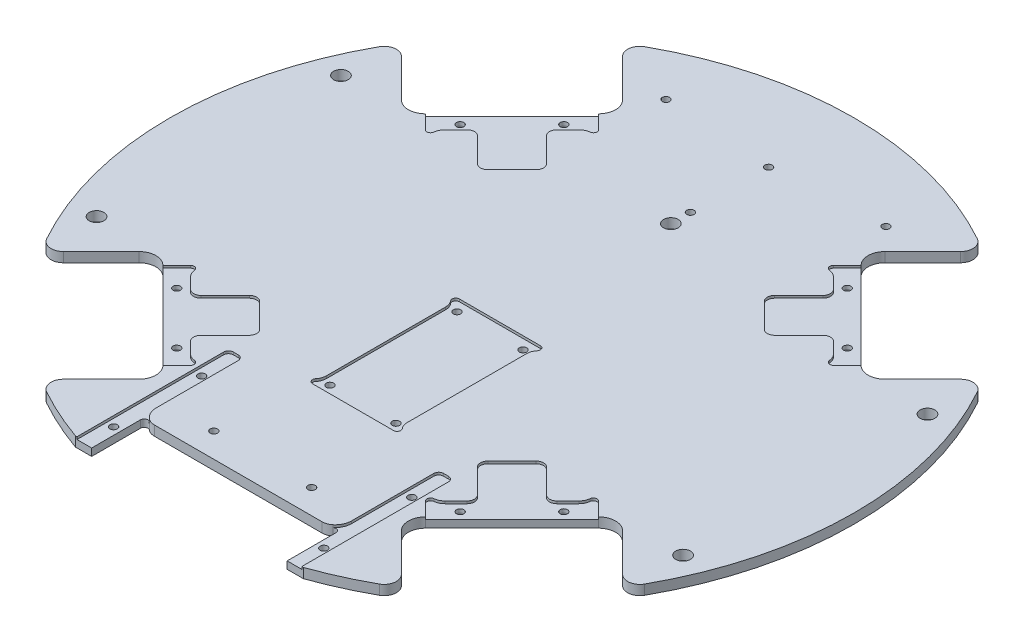
SolidWorks part; units mm, degrees
material "ABS PC"
ref_plane "Front Plane" through (0, 0, 0) normal (0, 0, 1) x (1, 0, 0)
ref_plane "Top Plane" through (0, 0, 0) normal (0, 1, 0) x (1, 0, 0)
ref_plane "Right Plane" through (0, 0, 0) normal (1, 0, 0) x (0, 0, -1)
sketch "Sketch1" plane through (0, 0, 0) normal (0, 1, 0) x (1, 0, 0)
  circle A0 centre (0, 0) radius 140
  dimension "D1" = 280
extrude "Boss-Extrude1" add sketch "Sketch1" along normal blind 4
sketch "Sketch7" plane through (0, 4, 0) normal (0, 1, 0) x (1, 0, 0)
  line L0 (-89.1308, -53.7048) -> (-53.7048, -89.1308)
  line L1 (-98.9596, -53.7048) -> (-121.6224, -76.3675)
  line L2 (-53.7048, -98.9596) -> (-76.3675, -121.6224)
  line L3 (-121.6224, -76.3675) -> (-76.3675, -121.6224)
  line L4 (0, 0) -> (-98.9949, -98.9949) construction
  line L7 (0, 0) -> (0, 130) construction
  circle A0 centre (0, 0) radius 140 construction
  arc A1 (-98.9596, -53.7048) -> (-89.1308, -53.7048) centre (-94.0452, -58.6192) cw
  arc A2 (-53.7048, -89.1308) -> (-53.7048, -98.9596) centre (-58.6192, -94.0452) cw
  dimension "D4" = 6.95
  dimension "D1" = 101
  dimension "D2" = 64
  dimension "D3" = 135
extrude "Cut-Extrude4" cut sketch "Sketch7" against normal up to next
sketch "Sketch8" plane through (0, 4, 0) normal (0, 1, 0) x (1, 0, 0)
  line L0 (-89.1308, -53.7048) -> (-53.7048, -89.1308)
  line L1 (-89.1308, -53.7048) -> (-83.474, -48.0479)
  line L2 (-53.7048, -89.1308) -> (-48.0479, -83.474)
  line L3 (-79.4765, -52.0454) -> (-52.0454, -79.4765)
  line L6 (-53.7048, -89.1308) -> (-89.1308, -53.7048) construction
  arc A0 (-83.474, -48.0479) -> (-80.9197, -48.9704) centre (-82.4133, -49.1086) cw
  arc A1 (-80.9197, -48.9704) -> (-79.4765, -52.0454) centre (-75.9409, -48.5099) ccw
  arc A2 (-48.0479, -83.474) -> (-48.9704, -80.9197) centre (-49.1086, -82.4133) ccw
  arc A3 (-48.9704, -80.9197) -> (-52.0454, -79.4765) centre (-48.5099, -75.9409) cw
  dimension "D2" = 1.5
  dimension "D3" = 5
  dimension "D4" = 1.5
  dimension "D5" = 5
  dimension "D1" = 8
extrude "Cut-Extrude5" cut sketch "Sketch8" against normal blind 1
sketch "Sketch14" plane through (0, 4, 0) normal (0, 1, 0) x (1, 0, 0)
  line L0 (-52.0454, -79.4765) -> (-79.4765, -52.0454) construction
  line L1 (-52.0454, -79.4765) -> (-79.4765, -52.0454) construction
  line L2 (-70.7107, -56.5685) -> (-60.8112, -46.669)
  line L3 (-56.5685, -70.7107) -> (-46.669, -60.8112)
  line L4 (-56.5685, -46.669) -> (-46.669, -56.5685)
  line L5 (-74.9533, -56.5685) -> (-56.5685, -74.9533)
  line L8 (-83.474, -48.0479) -> (-89.1308, -53.7048) construction
  arc A0 (-74.9533, -56.5685) -> (-70.7107, -56.5685) centre (-72.832, -54.4472) ccw
  arc A1 (-56.5685, -74.9533) -> (-56.5685, -70.7107) centre (-54.4472, -72.832) cw
  arc A2 (-60.8112, -46.669) -> (-56.5685, -46.669) centre (-58.6899, -48.7904) cw
  arc A3 (-46.669, -60.8112) -> (-46.669, -56.5685) centre (-48.7904, -58.6899) ccw
  dimension "D1" = 3
  dimension "D2" = 20
  dimension "D3" = 20
  dimension "D4" = 15.05
extrude "Cut-Extrude10" cut sketch "Sketch14" against normal up to surface (1 mm away) up to face at (-66.8825, 3, 66.8825)
sketch "Sketch9" plane through (0, 3, 0) normal (0, 1, 0) x (1, 0, 0)
  line L0 (-48.0479, -83.474) -> (-83.474, -48.0479) construction
  line L3 (-48.0479, -83.474) -> (-83.474, -48.0479) construction
  line L4 (-98.9596, -53.7048) -> (-119.0017, -73.7469) construction
  circle A0 centre (-79.196, -57.9828) radius 1.5
  circle A1 centre (-57.9828, -79.196) radius 1.5
  dimension "D4" = 3
  dimension "D1" = 4
  dimension "D2" = 30
  dimension "D3" = 17
  dimension "D5" = 4
extrude "Cut-Extrude6" cut sketch "Sketch9" against normal up to next
fillet "Fillet1" radius 5 2 edges at (-73.7469, 2, 119.0017) (-119.0017, 2, 73.7469)
pattern_circular "CirPattern1" count 4 over 360 about axis through (0, 4, 0) along (0, 1, 0) of "Cut-Extrude4", "Cut-Extrude6", "Fillet1", "Cut-Extrude5", "Cut-Extrude10"
sketch "Sketch2" plane through (0, 4, 0) normal (0, 1, 0) x (1, 0, 0)
  line L0 (-46.6476, -132) -> (-40, -132)
  line L1 (-40, -132) -> (-40, -112)
  line L2 (-34.3467, -112) -> (34.3467, -112)
  line L3 (40, -112) -> (40, -132)
  line L4 (40, -132) -> (46.6476, -132)
  line L5 (46.6476, -132) -> (46.6476, -140)
  line L6 (46.6476, -140) -> (-46.6476, -140)
  line L7 (-46.6476, -140) -> (-46.6476, -132)
  circle A0 centre (0, 0) radius 140 construction
  arc A1 (-40, -112) -> (-37.5415, -110.8462) centre (-38.5, -112) cw
  arc A2 (-34.3467, -112) -> (-37.5415, -110.8462) centre (-34.3467, -107) cw
  arc A3 (40, -112) -> (37.5415, -110.8462) centre (38.5, -112) ccw
  arc A4 (34.3467, -112) -> (37.5415, -110.8462) centre (34.3467, -107) ccw
  dimension "D5" = 1.5
  dimension "D6" = 5
  dimension "D1" = 8
  dimension "D2" = 20
  dimension "D3" = 80
  dimension "D4" = 6.6476
extrude "Cut-Extrude1" cut sketch "Sketch2" against normal up to next
sketch "Sketch3" plane through (0, 4, 0) normal (0, 1, 0) x (1, 0, 0)
  line L0 (-40, -132) -> (-46.6476, -132) construction
  line L1 (-40, -132) -> (-46, -132)
  line L2 (-40, -132) -> (-40, -72)
  line L3 (-42, -70) -> (-44, -70)
  line L4 (-46, -132) -> (-46, -72)
  line L5 (40, -132) -> (46, -132)
  line L6 (40, -132) -> (40, -72)
  line L7 (42, -70) -> (44, -70)
  line L8 (46, -132) -> (46, -72)
  line L12 (-40, -112) -> (-40, -132) construction
  line L13 (40, -132) -> (40, -112) construction
  arc A0 (40, -72) -> (42, -70) centre (42, -72) cw
  arc A1 (44, -70) -> (46, -72) centre (44, -72) cw
  arc A2 (-40, -72) -> (-42, -70) centre (-42, -72) ccw
  arc A3 (-44, -70) -> (-46, -72) centre (-44, -72) ccw
  dimension "D5" = 2
  dimension "D1" = 6
  dimension "D2" = 62
extrude "Cut-Extrude2" cut sketch "Sketch3" against normal blind 1
sketch "Sketch18" plane through (0, 4, 0) normal (0, 1, 0) x (1, 0, 0)
  line L0 (-40, -112) -> (-40, -72) construction
  line L1 (-40, -112) -> (-40, -72) construction
  line L3 (-40, -105.608) -> (-40, -112)
  line L4 (-40, -112) -> (-37.5415, -110.8462)
  line L5 (40, -72) -> (40, -112) construction
  line L6 (40, -105.608) -> (40, -112)
  line L7 (40, -112) -> (37.5415, -110.8462)
  arc A0 (-37.5415, -110.8462) -> (-40, -105.608) centre (-33.1904, -105.608) cw
  arc A2 (-37.5415, -110.8462) -> (-34.3467, -112) centre (-34.3467, -107) ccw construction
  arc A3 (37.5415, -110.8462) -> (40, -105.608) centre (33.1904, -105.608) ccw
  arc A4 (34.3467, -112) -> (37.5415, -110.8462) centre (34.3467, -107) ccw construction
extrude "Cut-Extrude14" cut sketch "Sketch18" against normal up to surface (1 mm away) up to face at (42.5714, 3, 94.1674)
fillet "Fillet3" radius 1.5 8 edges at (57.9828, 0, 80.696) (79.196, 0, 59.4828) (79.196, 0, -56.4828) (57.9828, 0, -77.696) (-57.9828, 0, -77.696) (-79.196, 0, -56.4828) (-57.9828, 0, 80.696) (-79.196, 0, 59.4828)
sketch "Sketch10" plane through (0, 4, 0) normal (0, 1, 0) x (1, 0, 0)
  circle A0 centre (-13.5, -61) radius 1.5
  circle A1 centre (13.5, -61) radius 1.5
  circle A2 centre (-13.5, -9) radius 1.5
  circle A3 centre (13.5, -9) radius 1.5
  dimension "D3" = 3
  dimension "D1" = 13.5
  dimension "D2" = 27
  dimension "D4" = 61
  dimension "D5" = 52
extrude "Cut-Extrude7" cut sketch "Sketch10" against normal up to next
sketch "Sketch11" plane through (0, 4, 0) normal (0, 1, 0) x (1, 0, 0)
  line L0 (34.3467, -112) -> (-34.3467, -112) construction
  circle A0 centre (-20, -102) radius 1.5
  circle A1 centre (20, -102) radius 1.5
  dimension "D1" = 3
  dimension "D2" = 40
  dimension "D3" = 10
  dimension "D4" = 20
extrude "Cut-Extrude8" cut sketch "Sketch11" against normal up to next
sketch "Sketch13" plane through (0, 4, 0) normal (0, 1, 0) x (1, 0, 0)
  line L0 (-46, -132) -> (-40, -132) construction
  line L4 (-40, -105.608) -> (-40, -72) construction
  line L5 (40, -72) -> (40, -105.608) construction
  circle A0 centre (-43, -84) radius 1.5
  circle A1 centre (-43, -120) radius 1.5
  circle A2 centre (43, -120) radius 1.5
  circle A3 centre (43, -84) radius 1.5
  dimension "D1" = 3
  dimension "D2" = 12
  dimension "D3" = 36
  dimension "D4" = 3
  dimension "D5" = 3
extrude "Cut-Extrude9" cut sketch "Sketch13" against normal up to next
sketch "Sketch15" plane through (0, 4, 0) normal (0, 1, 0) x (1, 0, 0)
  line L1 (-16.55, -4.95) -> (16.55, -4.95)
  line L2 (-16.55, -10.6033) -> (-16.55, -59.3967)
  line L3 (-16.55, -65.05) -> (16.55, -65.05)
  line L4 (16.55, -10.6033) -> (16.55, -59.3967)
  circle A0 centre (-13.5, -61) radius 1.5 construction
  circle A1 centre (-13.5, -9) radius 1.5 construction
  arc A2 (-16.55, -4.95) -> (-17.7038, -7.4085) centre (-16.55, -6.45) ccw
  arc A3 (-16.55, -10.6033) -> (-17.7038, -7.4085) centre (-21.55, -10.6033) ccw
  arc A4 (16.55, -4.95) -> (17.7038, -7.4085) centre (16.55, -6.45) cw
  arc A5 (17.7038, -7.4085) -> (16.55, -10.6033) centre (21.55, -10.6033) ccw
  arc A6 (-16.55, -65.05) -> (-17.7038, -62.5915) centre (-16.55, -63.55) cw
  arc A7 (-17.7038, -62.5915) -> (-16.55, -59.3967) centre (-21.55, -59.3967) ccw
  arc A8 (16.55, -65.05) -> (17.7038, -62.5915) centre (16.55, -63.55) ccw
  arc A9 (17.7038, -62.5915) -> (16.55, -59.3967) centre (21.55, -59.3967) cw
  dimension "D3" = 4.05
  dimension "D5" = 1.5
  dimension "D6" = 5
  dimension "D1" = 33.1
  dimension "D2" = 4.05
  dimension "D4" = 16.55
extrude "Cut-Extrude11" cut sketch "Sketch15" against normal blind 1
sketch "Sketch16" plane through (0, 4, 0) normal (0, 1, 0) x (1, 0, 0)
  circle A0 centre (0, 73) radius 1.5
  circle A1 centre (-45, 108) radius 1.5
  circle A2 centre (45, 108) radius 1.5
  circle A3 centre (0, 105) radius 1.5
  circle A4 centre (0, 65) radius 3
  dimension "D2" = 3
  dimension "D5" = 6
  dimension "D1" = 73
  dimension "D3" = 108
  dimension "D4" = 90
  dimension "D6" = 32
  dimension "D7" = 65
extrude "Cut-Extrude12" cut sketch "Sketch16" against normal up to next
sketch "Sketch17" plane through (0, 4, 0) normal (0, 1, 0) x (1, 0, 0)
  circle A0 centre (-120, 50) radius 3
  circle A1 centre (-120, -50) radius 3
  circle A2 centre (120, 50) radius 3
  circle A3 centre (120, -50) radius 3
  dimension "D1" = 6
  dimension "D2" = 50
  dimension "D3" = 50
  dimension "D4" = 120
  dimension "D5" = 120
extrude "Cut-Extrude13" cut sketch "Sketch17" against normal up to next
